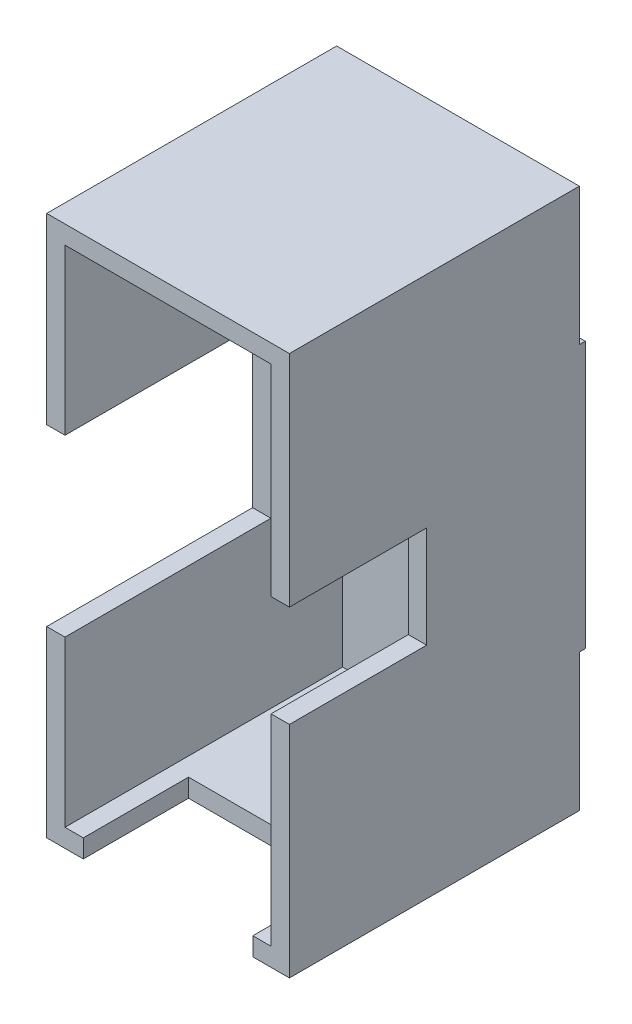
SolidWorks part; units mm, degrees
ref_plane "Front Plane" through (0, 0, 0) normal (0, 0, 1) x (1, 0, 0)
ref_plane "Top Plane" through (0, 0, 0) normal (0, 1, 0) x (1, 0, 0)
ref_plane "Right Plane" through (0, 0, 0) normal (1, 0, 0) x (0, 0, -1)
sketch "Sketch1" plane through (0, 0, 0) normal (0, 0, 1) x (1, 0, 0)
  line L1 (-22.525, -55.1) -> (22.525, -55.1)
  line L2 (-22.525, -55.1) -> (-22.525, 55.1)
  line L3 (-22.525, 55.1) -> (22.525, 55.1)
  line L4 (22.525, -55.1) -> (22.525, 55.1)
  line L5 (-22.525, -55.1) -> (22.525, 55.1) construction
  line L6 (-22.525, 55.1) -> (22.525, -55.1) construction
  line L7 (-26.525, 59.1) -> (26.525, 59.1)
  line L8 (-26.525, 59.1) -> (-26.525, -59.1)
  line L9 (-26.525, -59.1) -> (26.525, -59.1)
  line L10 (26.525, 59.1) -> (26.525, -59.1)
  line L11 (-26.525, 59.1) -> (26.525, -59.1) construction
  line L12 (-26.525, -59.1) -> (26.525, 59.1) construction
  point P0 (0, 0)
  point P6 (0, 0)
  dimension "D1" = 45.05
  dimension "D2" = 110.2
  dimension "D3" = 4
  dimension "D4" = 4
extrude "Boss-Extrude1" add sketch "Sketch1" along normal blind 60.67
sketch "Sketch2" plane through (0, 0, 0) normal (0, 0, 1) x (1, 0, 0)
  line L1 (-26.525, -59.1) -> (26.525, -59.1)
  line L2 (-26.525, -59.1) -> (-26.525, 59.1)
  line L3 (-26.525, 59.1) -> (26.525, 59.1)
  line L4 (26.525, -59.1) -> (26.525, 59.1)
  line L5 (-26.525, -59.1) -> (26.525, 59.1) construction
  line L6 (-26.525, 59.1) -> (26.525, -59.1) construction
  point P0 (0, 0)
extrude "Boss-Extrude2" add sketch "Sketch2" against normal blind 4 contours L2 L1 L4 L3
sketch "Sketch3" plane through (26.525, 0, 0) normal (1, 0, 0) x (0, 0, -1)
  line L0 (-60.67, -59.1) -> (-60.67, 59.1) construction
  line L1 (-60.67, 11.1) -> (-30.67, 11.1)
  line L2 (-60.67, 11.1) -> (-60.67, -11.1)
  line L3 (-60.67, -11.1) -> (-30.67, -11.1)
  line L4 (-30.67, 11.1) -> (-30.67, -11.1)
  line L5 (-60.67, 59.1) -> (4, 59.1) construction
  line L6 (-60.67, -59.1) -> (4, -59.1) construction
  dimension "D1" = 48
  dimension "D2" = 48
  dimension "D3" = 30
extrude "Cut-Extrude1" cut sketch "Sketch3" against normal blind 4
sketch "Sketch4" plane through (-26.525, 0, 0) normal (-1, 0, 0) x (0, 0, 1)
  line L6 (60.67, -59.1) -> (-4, -59.1) construction
  line L8 (28.335, -59.1) -> (28.335, 63.777) construction
  line L9 (60.67, -19.1) -> (15.67, -19.1)
  line L10 (15.67, 19.1) -> (15.67, -19.1)
  line L11 (60.67, 19.1) -> (15.67, 19.1)
  line L12 (60.67, 19.1) -> (60.67, -19.1)
  line L13 (60.67, 59.1) -> (-4, 59.1) construction
  line L14 (60.67, 59.1) -> (60.67, -59.1) construction
  dimension "D1" = 45
  dimension "D2" = 40
  dimension "D3" = 40
extrude "Cut-Extrude2" cut sketch "Sketch4" against normal blind 4
sketch "Sketch5" plane through (0, -59.1, 0) normal (0, -1, 0) x (1, 0, 0)
  line L0 (-26.525, 60.67) -> (26.525, 60.67) construction
  line L1 (-18.525, 60.67) -> (18.525, 60.67)
  line L2 (-18.525, 60.67) -> (-18.525, 37.67)
  line L3 (-18.525, 37.67) -> (18.525, 37.67)
  line L4 (18.525, 60.67) -> (18.525, 37.67)
  line L5 (26.525, 60.67) -> (26.525, -4) construction
  line L6 (-26.525, 60.67) -> (-26.525, -4) construction
  dimension "D1" = 23
  dimension "D2" = 8
  dimension "D3" = 8
extrude "Cut-Extrude3" cut sketch "Sketch5" against normal blind 4
sketch "Sketch6" plane through (0, 0, 0) normal (0, 0, 1) x (1, 0, 0)
  circle A0 centre (0, 0) radius 11.5
  circle A1 centre (0, 0) radius 13.5
  dimension "D1" = 23
  dimension "D2" = 27
extrude "Boss-Extrude3" add sketch "Sketch6" along normal blind 3.4
sketch "Sketch8" plane through (0, 0, 3.4) normal (0, 0, 1) x (1, 0, 0)
  circle A0 centre (0, 0) radius 13.5
  dimension "D1" = 27
sketch "Sketch9" plane through (0, 0, -4) normal (0, 0, -1) x (-1, 0, 0)
  circle A0 centre (0, 0) radius 11.5
  dimension "D1" = 23
extrude "Cut-Extrude4" cut sketch "Sketch9" against normal blind 5.5
sketch "Sketch10" plane through (26.525, 0, 0) normal (1, 0, 0) x (0, 0, -1)
  line L0 (0, 0) -> (22.7501, 0) construction
  line L1 (4, -59.1) -> (2.7, -59.1)
  line L2 (4, -59.1) -> (4, -29.1)
  line L3 (4, -29.1) -> (2.7, -29.1)
  line L4 (2.7, -59.1) -> (2.7, -29.1)
  line L5 (4, 29.1) -> (2.7, 29.1)
  line L6 (2.7, 59.1) -> (2.7, 29.1)
  line L7 (4, 59.1) -> (2.7, 59.1)
  line L8 (4, 59.1) -> (4, 29.1)
  line M16 (4, -59.1) -> (4, 59.1)
  line M17 (4, 59.1) -> (-60.67, 59.1)
  dimension "D1" = 30
  dimension "D2" = 1.3
extrude "Cut-Extrude6" cut sketch "Sketch10" against normal through all contours L6 L5 M17 M16 | L2 L1 L4 L3 region at (26.525, 44.1, -3.35)
extrude "Boss-Extrude5" add sketch "Sketch8" along normal blind 3
sketch "Sketch12" plane through (0, 0, 6.4) normal (0, 0, 1) x (1, 0, 0)
  circle A0 centre (0, 0) radius 3.325
  dimension "D1" = 6.65
extrude "Cut-Extrude8" cut sketch "Sketch12" against normal through all
